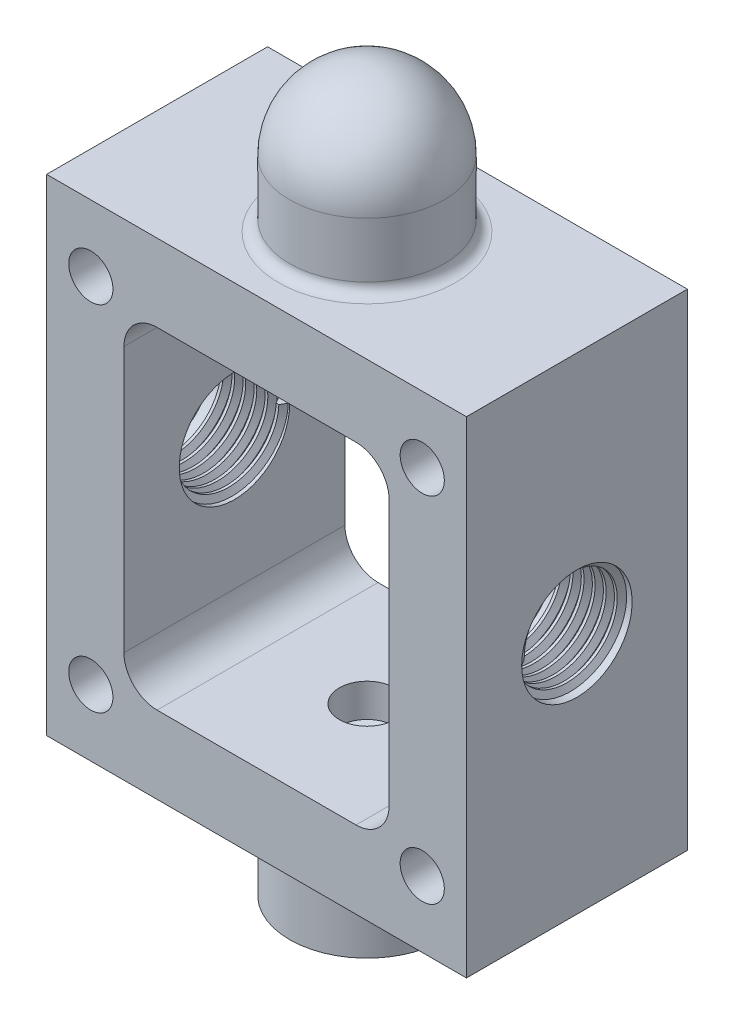
SolidWorks part; units mm, degrees
ref_plane "Front Plane" through (0, 0, 0) normal (0, 0, 1) x (1, 0, 0)
ref_plane "Top Plane" through (0, 0, 0) normal (0, 1, 0) x (1, 0, 0)
ref_plane "Right Plane" through (0, 0, 0) normal (1, 0, 0) x (0, 0, -1)
sketch "Sketch1" plane through (0, 0, 0) normal (0, 0, 1) x (1, 0, 0)
  line L1 (0, 0) -> (38, 0)
  line L2 (0, 0) -> (0, 44)
  line L3 (0, 44) -> (38, 44)
  line L4 (38, 0) -> (38, 44)
  line L5 (10, 37) -> (28, 37)
  line L6 (7, 34) -> (7, 10)
  line L7 (10, 7) -> (28, 7)
  line L8 (31, 34) -> (31, 10)
  arc A0 (28, 7) -> (31, 10) centre (28, 10) ccw
  arc A1 (7, 10) -> (10, 7) centre (10, 10) ccw
  arc A2 (10, 37) -> (7, 34) centre (10, 34) ccw
  arc A3 (28, 37) -> (31, 34) centre (28, 34) cw
  circle A4 centre (4, 38) radius 2
  circle A5 centre (4, 6) radius 2
  circle A6 centre (34, 6) radius 2
  circle A7 centre (34, 38) radius 2
  point P9 (19, 44)
  point P10 (19, 37)
  point P11 (7, 22)
  point P12 (0, 22)
  point P15 (31, 7)
  point P20 (7, 37)
  point P23 (31, 37)
  point P32 (3.9488, 40.2744)
  dimension "D5" = 3
  dimension "D6" = 4
  dimension "D1" = 38
  dimension "D2" = 44
  dimension "D3" = 30
  dimension "D4" = 24
  dimension "D7" = 4
  dimension "D8" = 6
  dimension "D9" = 6
  dimension "D10" = 4
extrude "Boss-Extrude1" add sketch "Sketch1" along normal blind 20
ref_plane "Plane1" through (0, 0, 10) normal (0, 0, 1) x (1, 0, 0)
sketch "Sketch2" plane through (0, 0, 10) normal (0, 0, 1) x (1, 0, 0)
  line L0 (19, 44) -> (19, 67.5872) construction
  line L1 (38, 44) -> (0, 44) construction
  line L2 (12, 44) -> (12, 50)
  line L3 (19, 57) -> (19, 44)
  line L4 (19, 44) -> (12, 44)
  arc A0 (12, 50) -> (19, 57) centre (19, 50) cw
  dimension "D1" = 7
  dimension "D2" = 13
  dimension "D3" = 7
revolve "Revolve1" add sketch "Sketch2" angle 360 about L3
fillet "Fillet1" radius 1 1 edges at (19, 44, 17)
sketch "Sketch3" plane through (0, 0, 10) normal (0, 0, 1) x (1, 0, 0)
  line L0 (19, 0) -> (19, -11.7842) construction
  line L1 (0, 0) -> (38, 0) construction
  line L2 (24, 0) -> (26, 0)
  line L3 (26, 0) -> (26, -8)
  line L4 (26, -8) -> (24, -8)
  line L5 (24, -8) -> (24, 0)
  point P1 (19, 0)
  dimension "D1" = 7
  dimension "D2" = 8
  dimension "D3" = 2
revolve "Revolve2" add sketch "Sketch3" angle 360 about L0
fillet "Fillet2" radius 1 1 edges at (19, 0, 17)
sketch "Sketch4" plane through (0, 0, 0) normal (0, -1, 0) x (1, 0, 0)
  circle A0 centre (19, 10) radius 5
extrude "Cut-Extrude1" cut sketch "Sketch4" against normal blind 4
sketch "Sketch5" plane through (0, 4, 0) normal (0, -1, 0) x (-1, 0, 0)
  circle A0 centre (-19, -10) radius 2.5
  dimension "D1" = 5
extrude "Cut-Extrude2" cut sketch "Sketch5" against normal blind 4
sketch "Sketch6" plane through (0, 37, 0) normal (0, -1, 0) x (1, 0, 0)
  circle A0 centre (19, 10) radius 1.75
  dimension "D1" = 3.5
extrude "Cut-Extrude3" cut sketch "Sketch6" against normal blind 13
sketch "Sketch7" plane through (0, 0, 0) normal (-1, 0, 0) x (0, 0, 1)
  line L0 (10, 44) -> (10, 40.9936) construction
  line L1 (20, 44) -> (0, 44) construction
  circle A0 centre (10, 22) radius 5
  dimension "D1" = 10
extrude "Cut-Extrude4" cut sketch "Sketch7" against normal through all
thread "Thread1" pitch 1 method extrude profile "Thread Profile1" start angle 0, offset 0, length 6, pitch 1, diameter 10
ref_plane "Plane2" through (38, 22, 15) normal (0, -1, 0) x (0, 0, 1)
sketch "Thread Profile1" plane through (38, 22, 15) normal (0, -1, 0) x (0, 0, 1)
  line L0 (0, 0) -> (0, 1) construction
  line L11 (0, 0) -> (0, 0.875)
  line L12 (0, 0.875) -> (-0.5413, 0.5625)
  line L13 (-0.5413, 0.5625) -> (-0.5413, 0.3125)
  line L15 (-0.5413, 0.3125) -> (0, 0)
  line L17 (-0.5413, 0.4375) -> (0, 0.4375) construction
  point P2 (0, 0)
  dimension "Pitch" = 1
  dimension "Profile_Angle" = 60
  dimension "Profile_Land" = 0.25
  dimension "Profile_Height" = 0.5413
thread "Thread2" pitch 1 method extrude profile "Thread Profile2" start angle 0, offset 0, length 6, pitch 1, diameter 10
ref_plane "Plane3" through (0, 22, 5) normal (0, -1, 0) x (0, 0, -1)
sketch "Thread Profile2" plane through (0, 22, 5) normal (0, -1, 0) x (0, 0, -1)
  line L0 (0, 0) -> (0, 1) construction
  line L11 (0, 0) -> (0, 0.875)
  line L12 (0, 0.875) -> (-0.5413, 0.5625)
  line L13 (-0.5413, 0.5625) -> (-0.5413, 0.3125)
  line L15 (-0.5413, 0.3125) -> (0, 0)
  line L17 (-0.5413, 0.4375) -> (0, 0.4375) construction
  point P2 (0, 0)
  dimension "Pitch" = 1
  dimension "Profile_Angle" = 60
  dimension "Profile_Land" = 0.25
  dimension "Profile_Height" = 0.5413
thread "Thread3" pitch 1 method extrude profile "Thread Profile3" start angle 0, offset 0, length 0, pitch 1, diameter 10
ref_plane "Plane4" through (24, -8, 10) normal (0, 0, 1) x (1, 0, 0)
sketch "Thread Profile3" plane through (24, -8, 10) normal (0, 0, 1) x (1, 0, 0)
  line L0 (0, 0) -> (0, 1) construction
  line L11 (0, 0) -> (0, 0.875)
  line L12 (0, 0.875) -> (-0.5413, 0.5625)
  line L13 (-0.5413, 0.5625) -> (-0.5413, 0.3125)
  line L15 (-0.5413, 0.3125) -> (0, 0)
  line L17 (-0.5413, 0.4375) -> (0, 0.4375) construction
  point P2 (0, 0)
  dimension "Pitch" = 1
  dimension "Profile_Angle" = 60
  dimension "Profile_Land" = 0.25
  dimension "Profile_Height" = 0.5413
